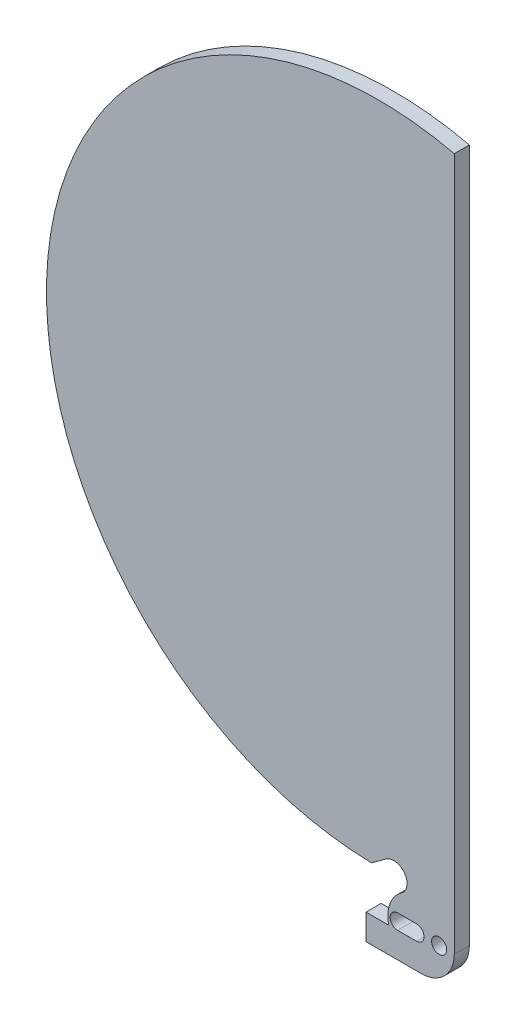
SolidWorks part; units mm, degrees
material "Zoltek Panex 33"
ref_plane "Front Plane" through (0, 0, 0) normal (0, 0, 1) x (1, 0, 0)
ref_plane "Top Plane" through (0, 0, 0) normal (0, 1, 0) x (1, 0, 0)
ref_plane "Right Plane" through (0, 0, 0) normal (1, 0, 0) x (0, 0, -1)
sketch "Sketch2" plane through (0, 0, 0) normal (0, 0, 1) x (1, 0, 0)
  line L0 (0, -2.5) -> (0, -4.6098) construction
  line L1 (-1, -2.5) -> (-5, -2.5) construction
  line L2 (0, -2.5) -> (0, 43.4177)
  line L3 (-3.125, -2) -> (-3.125, 0.6523) construction
  line L4 (-3.75, -2) -> (-2.5, -2)
  line L5 (-3.75, -3) -> (-2.5, -3)
  line L6 (-4.4, -2.5) -> (-4.4, -1.6286) construction
  line L7 (-10.0532, 0.9946) -> (5.0641, 0.9946) construction
  line L8 (-5.494, 0) -> (-4.517, 0.706)
  line L9 (-4.517, 0.706) -> (-3.4886, -0.7169) construction
  line L10 (-4.3424, -3) -> (-5.8424, -3)
  line L11 (-5.8424, -3) -> (-5.8424, -4.7)
  line L12 (-5.8424, -4.7) -> (-2.2, -4.7)
  line L13 (-2.5, -2) -> (-1, -2) construction
  line L14 (-2.5, -3) -> (-1, -3) construction
  circle A0 centre (-5.005, 21.9946) radius 21 construction
  arc A1 (-5.494, 0) -> (0, 43.4177) centre (-5.005, 21.9946) cw
  circle A2 centre (-1, -2.5) radius 0.5
  arc A3 (-3.75, -2) -> (-3.75, -3) centre (-3.75, -2.5) ccw
  circle A4 centre (-5, -2.5) radius 0.5 construction
  arc A5 (-2.5, -3) -> (-2.5, -2) centre (-2.5, -2.5) ccw
  arc A6 (-2.2, -4.7) -> (0, -2.5) centre (-2.2, -2.5) ccw
  arc A8 (-3.4886, -0.7169) -> (-4.517, 0.706) centre (-4.0028, -0.0054) ccw
  arc A9 (-3.4886, -0.7169) -> (-4.3424, -3) centre (-2.2, -2.5) ccw
  dimension "D1" = 42
  dimension "D2" = 2.5
  dimension "D3" = 0.6
  dimension "D4" = 5.005
  dimension "D5" = 1
  dimension "D6" = 4
  dimension "D7" = 0.5
  dimension "D9" = 1
  dimension "D8" = 1.5
  dimension "D12" = 1
  dimension "D10" = 1.5
  dimension "D13" = 1
  dimension "D14" = 1
  dimension "D15" = 1.25
extrude "Boss-Extrude1" add sketch "Sketch2" along normal mid plane 1
equation "\"pinSize\"= 1mm"
equation "\"D12@Sketch2\"=\"pinSize\""
equation "\"D13@Sketch2\"=\"pinSize\""
equation "\"D14@Sketch2\"=\"pinSize\""
